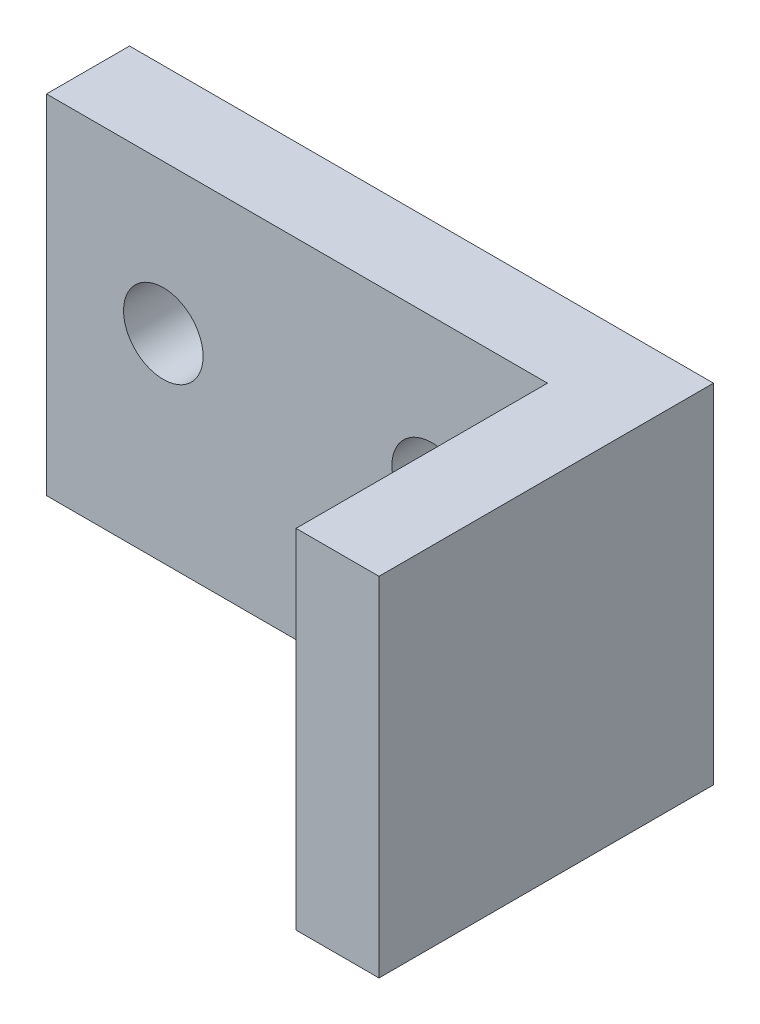
SolidWorks part; units mm, degrees
ref_plane "Ebene vorne" through (0, 0, 0) normal (0, 0, 1) x (1, 0, 0)
ref_plane "Ebene oben" through (0, 0, 0) normal (0, 1, 0) x (1, 0, 0)
ref_plane "Ebene rechts" through (0, 0, 0) normal (1, 0, 0) x (0, 0, -1)
sketch "Skizze1" plane through (0, 0, 0) normal (0, 1, 0) x (1, 0, 0)
  line L1 (-12.6, 12.65) -> (25.15, 12.65)
  line L2 (25.15, 12.65) -> (25.15, -12.65)
  line L3 (25.15, -12.65) -> (-12.6, -12.65)
  line L5 (-12.6, 10.85) -> (23.35, 10.85)
  line L6 (23.35, 10.85) -> (23.35, -10.85)
  line L7 (23.35, -10.85) -> (-12.6, -10.85)
  arc A0 (-12.6, 12.65) -> (-12.6, -12.65) centre (-12.6, 0) ccw
  arc A1 (-12.6, 10.85) -> (-12.6, -10.85) centre (-12.6, 0) ccw
sketch "Skizze2" plane through (0, 0, 0) normal (0, 0, 1) x (1, 0, 0)
  line L0 (0, 170) -> (0, 640)
sketch "Skizze3" plane through (0, 0, 0) normal (0, 0, 1) x (1, 0, 0)
  line L13 (-11, 155) -> (11, 155)
  line L15 (11, 155) -> (11, 130)
  line L17 (11, 130) -> (33.5, 130)
  line L18 (33.5, 130) -> (33.5, 205)
  line L19 (33.5, 205) -> (-33.5, 205)
  line L23 (-33.5, 130) -> (-33.5, 205)
  line L24 (-11, 130) -> (-33.5, 130)
  line L25 (-11, 155) -> (-11, 130)
  point P16 (0, 205)
  point P19 (0, 155)
sketch "Skizze4" plane through (0, 0, 0) normal (0, 1, 0) x (1, 0, 0)
  line L0 (25.15, -12.65) -> (33.5, -12.65)
  line L1 (33.5, -12.65) -> (33.5, 21)
  line L2 (33.5, 21) -> (-25.25, 21)
  line L3 (25.15, -12.65) -> (25.15, 12.65)
  line L4 (25.15, 12.65) -> (-25.25, 12.65)
  line L5 (-25.25, 12.65) -> (-25.25, 21)
extrude "Aufsatz-Linear austragen1" add sketch "Skizze4" along normal up to vertex (205 mm away) from vertex up to point (33.5, 205, 0) starting at point (0, 170, 0)
sketch "Holes" plane through (0, 0, 0) normal (0, 0, 1) x (1, 0, 0)
  circle A0 centre (13.5, 190) radius 4
  circle A1 centre (-13.5, 190) radius 4
sketch "Skizze6" plane through (0, 0, 0) normal (0, 0, 1) x (1, 0, 0)
  circle A0 centre (-13.5, 190) radius 4
  circle A1 centre (13.5, 190) radius 4
extrude "Schnitt-Linear austragen1" cut sketch "Skizze6" against normal up to surface (21 mm away) up to face at (4.125, 187.5, -21)
